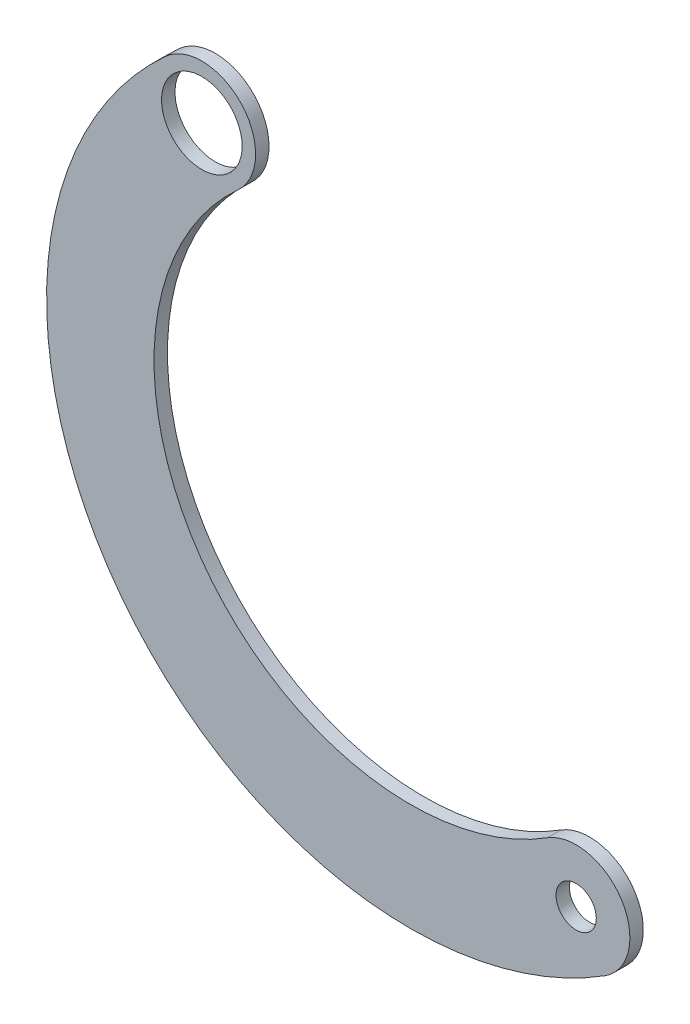
SolidWorks part; units mm, degrees
ref_plane "Front Plane" through (0, 0, 0) normal (0, 0, 1) x (1, 0, 0)
ref_plane "Top Plane" through (0, 0, 0) normal (0, 1, 0) x (1, 0, 0)
ref_plane "Right Plane" through (0, 0, 0) normal (1, 0, 0) x (0, 0, -1)
sketch "Esquisse1" plane through (0, 0, 0) normal (0, 0, 1) x (1, 0, 0)
  line L0 (8.3805, -12.0903) -> (6.7893, -13.302) construction
  line L1 (-7.1443, 4.997) -> (20.723, -31.6009) construction
  arc A0 (-7.1443, 4.997) -> (20.723, -31.6009) centre (8.3805, -12.0903) ccw construction
  arc A1 (-9.8342, 7.9576) -> (22.8614, -34.9813) centre (8.3805, -12.0903) ccw
  arc A2 (-4.4545, 2.0365) -> (18.5846, -28.2205) centre (8.3805, -12.0903) ccw
  arc A3 (-4.4545, 2.0365) -> (-9.8342, 7.9576) centre (-7.1443, 4.997) ccw
  arc A4 (22.8614, -34.9813) -> (18.5846, -28.2205) centre (20.723, -31.6009) ccw
  circle A5 centre (20.723, -31.6009) radius 1.5
  circle A6 centre (-7.1443, 4.997) radius 3
  point P3 (-9.9875, -26.0766)
  dimension "D2" = 8
  dimension "D3" = 6
  dimension "D4" = 3
  dimension "D1" = 2
base flange "Tôle de base pliée1" sketch "Esquisse1" thickness 1 reverse thickness direction yes parameters "D1"=0.7366
sketch "Bend-Lines1" [suppressed] plane through (0, 0, 0) normal (0, 1, 0) x (1, 0, 0)
sketch "Bounding-Box1" [suppressed] plane through (0, 0, 0) normal (0, 1, 0) x (1, 0, 0)
sheet metal parameters "Sheet-Metal1" thickness 1 parameters "D1"=0.7366
flat pattern "Flat-Pattern1" [suppressed]
sketch "Bend-Lines2" plane through (0, 0, 0) normal (0, 1, 0) x (1, 0, 0)
sketch3d "Bounding-Box2" [suppressed]
  line L0 (7.0034, 14.1492, 0) -> (-25.7103, -28.8133, 0) construction
  line L1 (30.1449, -3.4718, 0) -> (-2.5688, -46.4344, 0) construction
  line L2 (7.0034, 14.1492, 0) -> (30.1449, -3.4718, 0) construction
  line L3 (-25.7103, -28.8133, 0) -> (-2.5688, -46.4344, 0) construction
